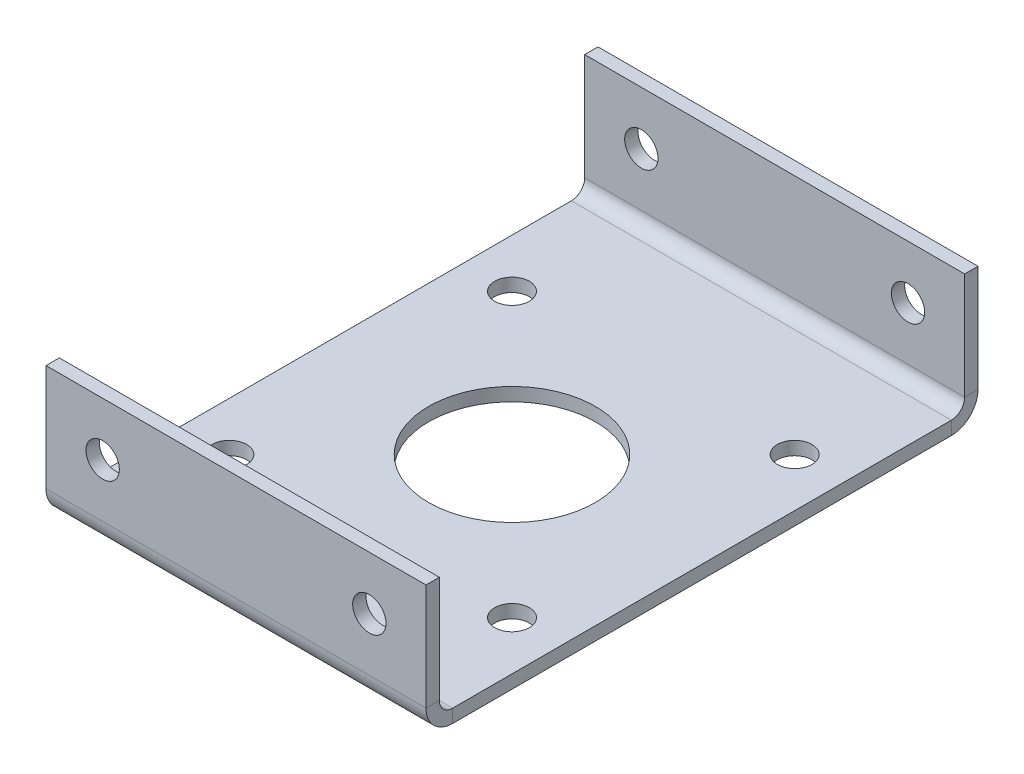
SolidWorks part; units mm, degrees
note: The reader was unsure of these and kept them because the rebuilt part matched: flange length of "Edge-Flange1".
ref_plane "Front Plane" through (0, 0, 0) normal (0, 0, 1) x (1, 0, 0)
ref_plane "Top Plane" through (0, 0, 0) normal (0, 1, 0) x (1, 0, 0)
ref_plane "Right Plane" through (0, 0, 0) normal (1, 0, 0) x (0, 0, -1)
sketch "Sketch1" plane through (0, 0, 0) normal (0, 1, 0) x (1, 0, 0)
  line L1 (-18.0975, 25.019) -> (18.0975, 25.019)
  line L2 (-18.0975, 25.019) -> (-18.0975, -25.019)
  line L3 (-18.0975, -25.019) -> (18.0975, -25.019)
  line L4 (18.0975, 25.019) -> (18.0975, -25.019)
  line L5 (-18.0975, 25.019) -> (18.0975, -25.019) construction
  line L6 (-18.0975, -25.019) -> (18.0975, 25.019) construction
  circle A0 centre (0, 0) radius 7.9375
  point P0 (0, 0)
  dimension "D3" = 15.875
  dimension "D1" = 36.195
  dimension "D2" = 50.038
base flange "Base-Flange1" sketch "Sketch1" thickness 1.27 reverse thickness direction no parameters "D1"=1.27
edge flange "Edge-Flange1" sketch "Sketch8" flange angle 90 flange length 12.7 flange position material outside bend radius 1.27 thickness 1.27 relief rectangular parameters "D6"=10
sketch "Sketch8" plane through (0, 0, 25.019) normal (0, 0, 1) x (1, 0, 0)
  line L0 (-18.0975, 0) -> (18.0975, 0) construction
  line L1 (-18.0975, 0) -> (18.0975, 0)
  line L2 (-18.0975, 0) -> (-18.0975, 11.43)
  line L3 (-18.0975, 11.43) -> (18.0975, 11.43)
  line L4 (18.0975, 11.43) -> (18.0975, 0)
bend "EdgeBend1" bend radius 1.27 bend angle 90 parameters "D5"=1
mirror "Mirror1" about plane through (0, 0, 0) normal (0, 0, 1) of "Edge-Flange1"
bend "MirrorBend1" bend radius 1.27 bend angle 90 parameters "D5"=2
sketch "Sketch9" plane through (0, 0, 0) normal (0, 1, 0) x (1, 0, 0)
  line L0 (0, 0) -> (19.0381, 0) construction
  line L1 (0, 0) -> (13.462, 13.462) construction
  circle A0 centre (0, 0) radius 19.0381 construction
  circle A1 centre (13.462, 13.462) radius 1.651
  dimension "D1" = 26.924
  dimension "D2" = 3.302
  dimension "D3" = 45
extrude "Cut-Extrude1" cut sketch "Sketch9" against normal through all normal cut yes
sketch "Sketch10" plane through (0, 0, -26.289) normal (0, 0, -1) x (-1, 0, 0)
  line L0 (-18.0975, 6.35) -> (18.0975, 6.35) construction
  line L1 (-18.0975, 1.27) -> (-18.0975, 11.43) construction
  line L2 (18.0975, 11.43) -> (18.0975, 1.27) construction
  line L3 (0, 6.35) -> (0, 11.43) construction
  line L4 (-18.0975, 11.43) -> (18.0975, 11.43) construction
  line L5 (18.0975, 1.27) -> (-18.0975, 1.27) construction
  circle A0 centre (-12.7, 6.35) radius 1.5875
  circle A1 centre (12.7, 6.35) radius 1.5875
  dimension "D1" = 3.175
  dimension "D2" = 12.7
  dimension "D3" = 5.08
extrude "Cut-Extrude2" cut sketch "Sketch10" against normal through all both and the other way through all normal cut yes
pattern_circular "CirPattern2" count 4 over 360 about axis through (0, 0, 0) along (0, 1, 0) of "Cut-Extrude1"
sketch "Bend-Lines1" [suppressed] plane through (0, 0, 0) normal (0, 1, 0) x (1, 0, 0)
sketch "Bounding-Box1" [suppressed] plane through (0, 0, 0) normal (0, 1, 0) x (1, 0, 0)
sheet metal parameters "Sheet-Metal1" thickness 1.27 parameters "D1"=1.27
flat pattern "Flat-Pattern1" [suppressed]
sketch "Bend-Lines2" plane through (0, 0, 0) normal (0, 1, 0) x (1, 0, 0)
sketch3d "Bounding-Box2" [suppressed]
  line L0 (18.0975, 22.225, 0) -> (18.0975, -22.225, 0) construction
  line L1 (-18.0975, 22.225, 0) -> (-18.0975, -22.225, 0) construction
  line L2 (18.0975, 22.225, 0) -> (-18.0975, 22.225, 0) construction
  line L3 (18.0975, -22.225, 0) -> (-18.0975, -22.225, 0) construction
sheet metal parameters "Sheet-Metal2" thickness 1.27 parameters "D1"=1.27
flat pattern "Flat-Pattern1"
sketch "Bend-Lines2" plane through (0, 0, 0) normal (0, 1, 0) x (1, 0, 0)
  line L0 (-18.0975, -22.4512) -> (18.0975, -22.4512) construction
  line L1 (-18.0975, -22.4512) -> (18.0975, -22.4512) construction
sketch3d "Bounding-Box2" [suppressed]
  line L0 (-18.0975, 22.225, 0) -> (-18.0975, -34.1074, 0) construction
  line L1 (18.0975, 22.225, 0) -> (18.0975, -34.1074, 0) construction
  line L2 (-18.0975, 22.225, 0) -> (18.0975, 22.225, 0) construction
  line L3 (-18.0975, -34.1074, 0) -> (18.0975, -34.1074, 0) construction
bend of the flat pattern "Flatten-<EdgeBend1>1"
sheet metal parameters "Sheet-Metal3" thickness 1.27 parameters "D1"=1.27
flat pattern "Flat-Pattern1"
sketch "Bend-Lines2" plane through (0, 0, 0) normal (0, 1, 0) x (1, 0, 0)
  line L0 (-18.0975, -22.4512) -> (18.0975, -22.4512) construction
  line L1 (-18.0975, -22.4512) -> (18.0975, -22.4512) construction
  line L2 (18.0975, 22.4512) -> (-18.0975, 22.4512) construction
  line L3 (18.0975, 22.4512) -> (-18.0975, 22.4512) construction
sketch3d "Bounding-Box2" [suppressed]
  line L0 (-18.0975, 34.1074, 0) -> (-18.0975, -34.1074, 0) construction
  line L1 (18.0975, 34.1074, 0) -> (18.0975, -34.1074, 0) construction
  line L2 (-18.0975, 34.1074, 0) -> (18.0975, 34.1074, 0) construction
  line L3 (-18.0975, -34.1074, 0) -> (18.0975, -34.1074, 0) construction
bend of the flat pattern "Flatten-<EdgeBend1>1"
bend of the flat pattern "Flatten-<MirrorBend1>1"
sheet metal parameters "Sheet-Metal4" thickness 1.27 parameters "D1"=1.27
flat pattern "Flat-Pattern1"
sketch "Bend-Lines2" plane through (0, 0, 0) normal (0, 1, 0) x (1, 0, 0)
  line L0 (-18.0975, -22.4512) -> (18.0975, -22.4512) construction
  line L1 (-18.0975, -22.4512) -> (18.0975, -22.4512) construction
  line L2 (18.0975, 22.4512) -> (-18.0975, 22.4512) construction
  line L3 (18.0975, 22.4512) -> (-18.0975, 22.4512) construction
sketch3d "Bounding-Box2" [suppressed]
  line L0 (-18.0975, 34.1074, 0) -> (-18.0975, -34.1074, 0) construction
  line L1 (18.0975, 34.1074, 0) -> (18.0975, -34.1074, 0) construction
  line L2 (-18.0975, 34.1074, 0) -> (18.0975, 34.1074, 0) construction
  line L3 (-18.0975, -34.1074, 0) -> (18.0975, -34.1074, 0) construction
bend of the flat pattern "Flatten-<EdgeBend1>1"
bend of the flat pattern "Flatten-<MirrorBend1>1"
sheet metal parameters "Sheet-Metal6" thickness 1.27 parameters "D1"=1.27
flat pattern "Flat-Pattern1"
sketch "Bend-Lines2" plane through (0, 0, 0) normal (0, 1, 0) x (1, 0, 0)
  line L0 (-18.0975, -25.2452) -> (18.0975, -25.2452) construction
  line L1 (-18.0975, -25.2452) -> (18.0975, -25.2452) construction
  line L2 (18.0975, 25.2452) -> (-18.0975, 25.2452) construction
  line L3 (18.0975, 25.2452) -> (-18.0975, 25.2452) construction
sketch3d "Bounding-Box2" [suppressed]
  line L0 (-18.0975, 36.9014, 0) -> (-18.0975, -36.9014, 0) construction
  line L1 (18.0975, 36.9014, 0) -> (18.0975, -36.9014, 0) construction
  line L2 (-18.0975, 36.9014, 0) -> (18.0975, 36.9014, 0) construction
  line L3 (-18.0975, -36.9014, 0) -> (18.0975, -36.9014, 0) construction
bend of the flat pattern "Flatten-<EdgeBend1>1"
bend of the flat pattern "Flatten-<MirrorBend1>1"
sheet metal parameters "Sheet-Metal7" thickness 1.27 parameters "D1"=1.27
flat pattern "Flat-Pattern1"
sketch "Bend-Lines2" plane through (0, 0, 0) normal (0, 1, 0) x (1, 0, 0)
  line L0 (-18.0975, -25.2452) -> (18.0975, -25.2452) construction
  line L1 (-18.0975, -25.2452) -> (18.0975, -25.2452) construction
  line L2 (18.0975, 25.2452) -> (-18.0975, 25.2452) construction
  line L3 (18.0975, 25.2452) -> (-18.0975, 25.2452) construction
sketch3d "Bounding-Box2" [suppressed]
  line L0 (-18.0975, 36.9014, 0) -> (-18.0975, -36.9014, 0) construction
  line L1 (18.0975, 36.9014, 0) -> (18.0975, -36.9014, 0) construction
  line L2 (-18.0975, 36.9014, 0) -> (18.0975, 36.9014, 0) construction
  line L3 (-18.0975, -36.9014, 0) -> (18.0975, -36.9014, 0) construction
bend of the flat pattern "Flatten-<EdgeBend1>1"
bend of the flat pattern "Flatten-<MirrorBend1>1"
